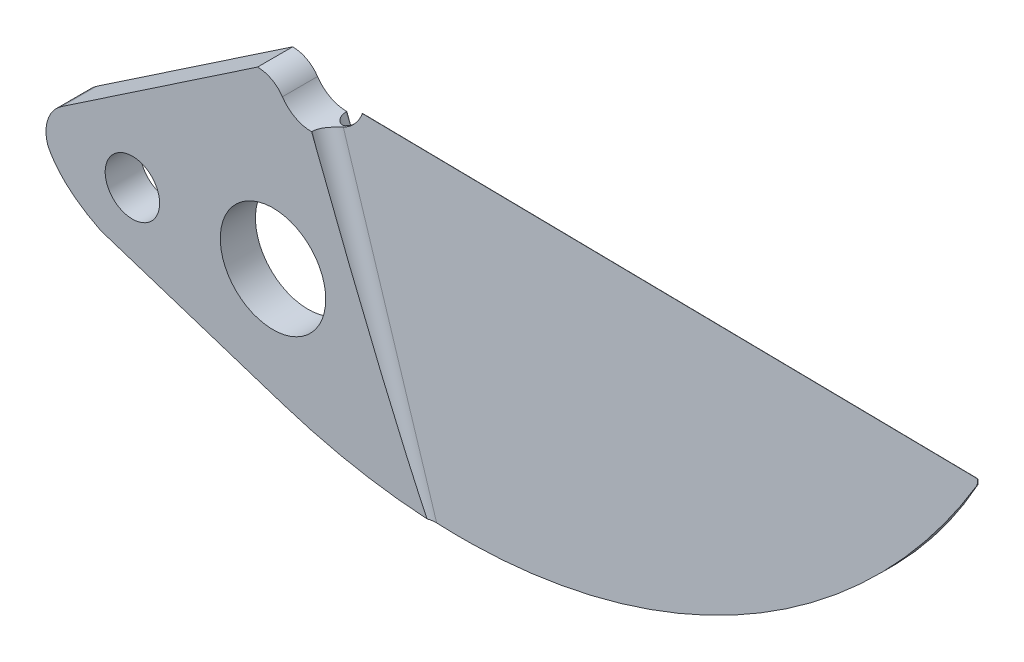
SolidWorks part; units mm, degrees
note: The reader was unsure of these and kept them because the rebuilt part matched: shared geometry of "Schizzo1<4>".
ref_plane "Piano frontale" through (0, 0, 0) normal (0, 0, 1) x (1, 0, 0)
ref_plane "Piano superiore" through (0, 0, 0) normal (0, 1, 0) x (1, 0, 0)
ref_plane "Piano destro" through (0, 0, 0) normal (1, 0, 0) x (0, 0, -1)
sketch "Schizzo1" plane through (0, 0, 0) normal (0, 0, 1) x (1, 0, 0)
  line L0 (-19.1309, 9.5) -> (-0.88, 9.5)
  line L2 (2.2, 7.8503) -> (2.2, -13.5762) construction
  line L7 (-9.8, -3.0189) -> (0.5947, -6.3963)
  line L8 (2.2, 7.8503) -> (8.2483, -7.9062) construction
  line L9 (39.0913, 8.7) -> (39.0913, 8.4)
  line L16 (2.2, 7.8503) -> (8.2483, -7.9062)
  line L17 (-20.2457, 6.9963) -> (-15.9603, 2.237)
  line L20 (-15.9603, 2.237) -> (-14.8391, 1.1157)
  line L21 (8.2483, -7.9062) -> (2.2, 7.8503)
  line L22 (0, 0) -> (0, 35.2311) construction
  line L23 (0, 0) -> (52.0689, 0) construction
  line L25 (4.0913, 9.2) -> (39.0913, 8.7)
  line L26 (-0.88, 9.5) -> (50.6514, 9.5) construction
  circle A6 centre (0, 0) radius 3
  arc A15 (0.5351, 8.742) -> (4.0913, 9.2) centre (2.2, 9.8503) ccw
  arc A16 (0.5351, 8.742) -> (-0.88, 9.5) centre (-0.88, 7.8) ccw
  arc A17 (-20.2457, 6.9963) -> (-19.1309, 9.5) centre (-19.1309, 8) cw
  arc A20 (0.5947, -6.3963) -> (39.0913, 8.4) centre (10.715, 24.7508) ccw
  arc A22 (-14.2826, 0.7232) -> (-12.8, -0.352) centre (-16.4271, -3.7936) cw
  arc A23 (-14.2826, 0.7232) -> (-14.8391, 1.1157) centre (-13.4249, 2.5299) cw
  spline S0 degree 2 poles (-9.8, -3.0189) (-12.0164, -1.9194) (-12.8, -0.352) knots 0 0 0 0.799119 0.799119 0.799119
  point P8 (-13.535, -0.1884)
  point P13 (-12.3576, -2.6848)
  point P21 (-22.5, 9.5)
  point P26 (-9.7338, -4.1393)
  dimension "D3" = 2
  dimension "D6" = 1.7
  dimension "D5" = 45
  dimension "D7" = 6
  dimension "D9" = 22.5
  dimension "D10" = 0.8
  dimension "D13" = 5
  dimension "D14" = 12
  dimension "D17" = 21
  dimension "D22" = 1.5
  dimension "D20" = 18.6271
  dimension "D8" = 0.88
  dimension "D18" = 35
  dimension "D19" = 9.5
  dimension "D23" = 65.5
  dimension "D27" = 15
  dimension "D28" = 0.3
  dimension "D4" = 2
  dimension "D15" = 13.2936
  dimension "D11" = 48
  dimension "D12" = 3.43
  dimension "D16" = 18
  dimension "D21" = 2.2
  dimension "D24" = 1.5857
  dimension "D25" = 24.7508
  dimension "D26" = 0.3
extrude "Estrusione-Estrusione1" add sketch "Schizzo1" along normal mid plane 2
extrude "Estrusione-Estrusione2" add sketch "Schizzo1<4>" along normal mid plane 1.9
sketch "Schizzo1<4>" plane through (0, 0, 0) normal (0, 0, 1) x (1, 0, 0) same geometry as "Schizzo1"
chamfer "Smusso1" distance 18 angle 3 1 edges at (21.5913, 8.95, 0.95)
chamfer "Smusso2" distance 18 angle 3 1 edges at (21.5913, 8.95, -0.95)
fillet "Raccordo1" radius 0.9 3 edges at (8.2483, -7.9062, 0.95) (3.3618, 8.2223, 0.0584) (5.2242, -0.028, 0.4894)
fillet "Raccordo2" radius 0.9 3 edges at (8.2483, -7.9062, -0.95) (26.0219, -4.202, -0.6925) (5.2242, -0.028, -0.4894)
sketch "Schizzo2" plane through (0, 0, 1) normal (0, 0, 1) x (1, 0, 0)
  line L0 (0, 0) -> (0, 15.0173) construction
  line L15 (-0.88, 9.5) -> (-30.88, -10.7353)
  line L20 (2.7977, 9.5) -> (-30.88, 9.5) construction
  line L21 (-0.88, 9.5) -> (-30.88, 9.5)
  line L22 (-30.88, 9.5) -> (-30.88, -10.7353)
  dimension "D1" = 56
  dimension "D2" = 30
extrude "Taglio-Estrusione1" cut sketch "Schizzo2" against normal blind 10
fillet "Raccordo3" radius 2 1 edges at (-14.0595, 0.6103, 0)
sketch "Schizzo3" plane through (0, 0, -1) normal (0, 0, -1) x (-1, 0, 0)
  line L0 (0, 0) -> (20.1722, 0) construction
  circle A0 centre (8, 0) radius 1.55
  dimension "D1" = 3.1
  dimension "D2" = 8
extrude "Taglio-Estrusione2" cut sketch "Schizzo3" against normal through all
